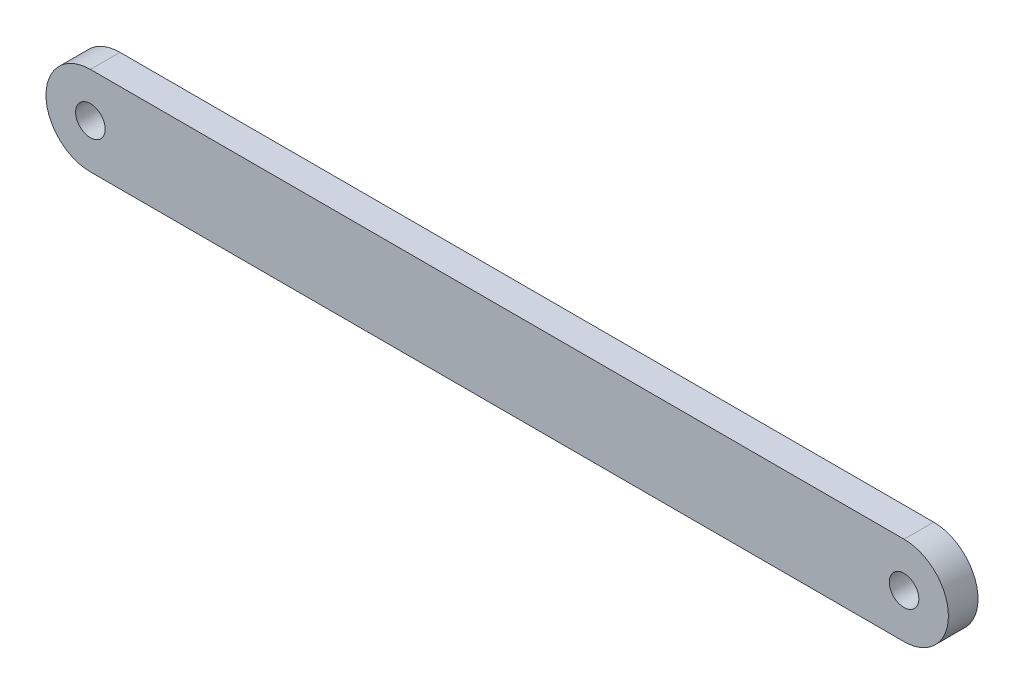
SolidWorks part; units mm, degrees
ref_plane "前视基准面" through (0, 0, 0) normal (0, 0, 1) x (1, 0, 0)
ref_plane "上视基准面" through (0, 0, 0) normal (0, 1, 0) x (1, 0, 0)
ref_plane "右视基准面" through (0, 0, 0) normal (1, 0, 0) x (0, 0, -1)
other "Configuration Table"
sketch "草图1" plane through (0, 0, 0) normal (0, 0, 1) x (1, 0, 0)
  line L0 (-1000, 0) -> (0, 0) construction
  line L2 (0, 1.5) -> (27.5, 1.5)
  line L3 (0, -1.5) -> (27.5, -1.5)
  line L4 (29, 0) -> (49000, 0) construction
  arc A0 (0, 1.5) -> (0, -1.5) centre (0, 0) ccw
  arc A1 (27.5, -1.5) -> (27.5, 1.5) centre (27.5, 0) ccw
  circle A2 centre (0, 0) radius 0.5
  circle A3 centre (27.5, 0) radius 0.5
  dimension "D1" = 3
  dimension "D3" = 1.5
  dimension "D4" = 1
  dimension "D5" = 1
  dimension "D2" = 27.5
extrude "凸台-拉伸1" add sketch "草图1" along normal blind 1
